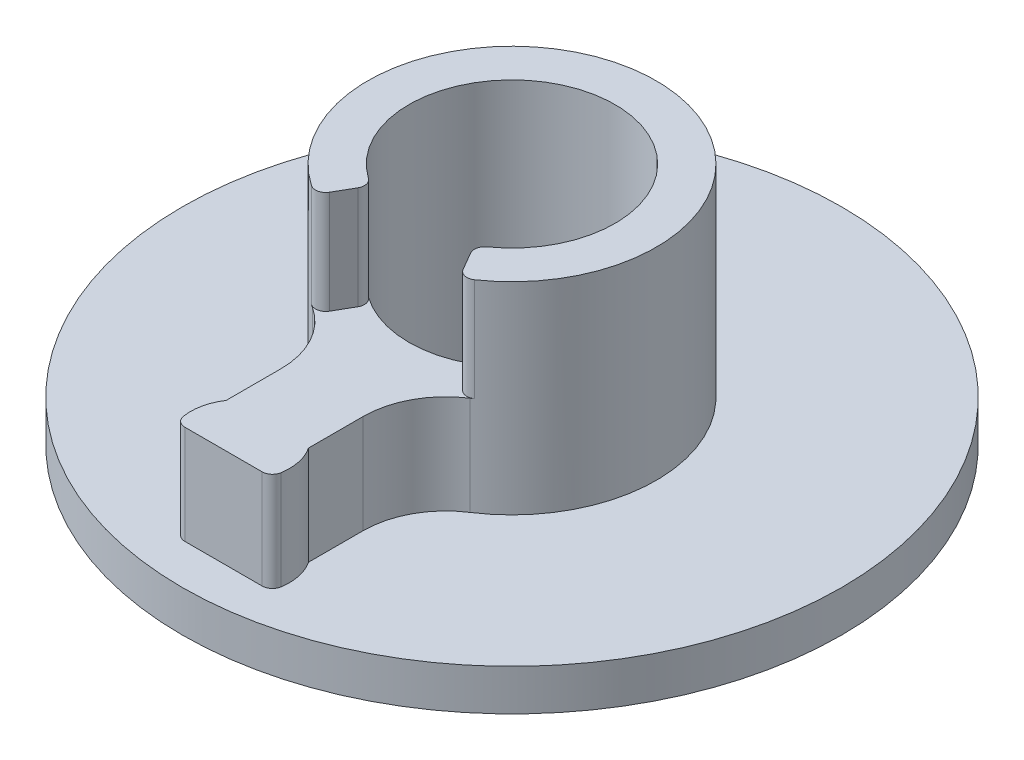
SolidWorks part; units mm, degrees
ref_plane "Plan de face" through (0, 0, 0) normal (0, 0, 1) x (1, 0, 0)
ref_plane "Plan de dessus" through (0, 0, 0) normal (0, 1, 0) x (1, 0, 0)
ref_plane "Plan de droite" through (0, 0, 0) normal (1, 0, 0) x (0, 0, -1)
sketch "Esquisse1" plane through (0, 0, 0) normal (0, 1, 0) x (1, 0, 0)
  line L18 (0, 9.2394) -> (0, -19.4288) construction
  circle A3 centre (0, 0) radius 2.5
  circle A7 centre (0, 0) radius 8
  point P1 (0, 0)
  point P2 (0, 0)
  point P3 (0, 0)
  point P4 (0, 0)
  point P5 (0, 0)
  point P7 (0, 0)
  point P8 (-1.5922, -5.6562)
  point P9 (1.577, -5.6853)
  point P10 (0, -8)
  point P11 (0, 0)
  point P12 (-0.0647, -8)
  point P30 (0, -8)
  point P31 (0, -8)
  dimension "D3" = 2.5
  dimension "D11" = 16
extrude "Boss.-Extru.1" add sketch "Esquisse1" along normal blind 1
sketch "Esquisse2" plane through (0, 1, 0) normal (0, 1, 0) x (1, 0, 0)
  line L0 (-1, -5.9367) -> (-1, -4.6098)
  line L1 (1, -5.9367) -> (1, -4.6098)
  line L2 (0, 5.8766) -> (0, -12.0862) construction
  line L3 (1.1314, -7) -> (-1.1314, -7)
  arc A0 (-1, -5.9367) -> (-1.1314, -7) centre (0, -6.6) ccw
  arc A1 (1.9091, -2.9335) -> (-1.9091, -2.9335) centre (0, 0) ccw
  circle A2 centre (0, 0) radius 2.5
  circle A3 centre (0, 0) radius 2.5 construction
  arc A4 (1.1314, -7) -> (1, -5.9367) centre (0, -6.6) ccw
  arc A5 (1.9091, -2.9335) -> (1, -4.6098) centre (3, -4.6098) ccw
  arc A6 (-1.9091, -2.9335) -> (-1, -4.6098) centre (-3, -4.6098) cw
  point P12 (0, 0)
  point P15 (0, 0)
  dimension "D4" = 1.2
  dimension "D6" = 2
  dimension "D1" = 7
  dimension "D2" = 7
  dimension "D3" = 6.6
  dimension "D5" = 1
extrude "Boss.-Extru.2" add sketch "Esquisse2" along normal blind 4.9
sketch "Esquisse4" plane through (0, 0, 0) normal (0, -1, 0) x (1, 0, 0)
  circle A0 centre (0, 0) radius 5.4
  circle A1 centre (0, 0) radius 4
  point P16 (0, 0)
  point P18 (0, 0)
  point P129 (0, 0)
  dimension "D1" = 8
  dimension "D2" = 10.8
extrude "Boss.-Extru.3" add sketch "Esquisse4" along normal blind 1.5
sketch "Esquisse5" plane through (0, 5.9, 0) normal (0, 1, 0) x (1, 0, 0)
  line L0 (-1.25, -2.1651) -> (-1.7569, -3.043)
  line L1 (1.25, -2.1651) -> (1.7569, -3.043)
  line L2 (0, 0) -> (0, -9.216) construction
  line L3 (-1, -5.9367) -> (-1, -4.6098)
  line L4 (1, -5.9367) -> (1, -4.6098)
  line L5 (0, 0) -> (-1.25, -2.1651) construction
  line L6 (0, 0) -> (1.25, -2.1651) construction
  line L8 (-1, -4.6098) -> (-1, -5.9367) construction
  line L9 (1, -5.9367) -> (1, -4.6098) construction
  line L10 (-1.1314, -7) -> (1.1314, -7)
  arc A0 (-1, -5.9367) -> (-1.1314, -7) centre (0, -6.6) ccw
  arc A1 (-1.25, -2.1651) -> (1.25, -2.1651) centre (0, 0) ccw
  circle A2 centre (0, 0) radius 2.5 construction
  arc A4 (1.1314, -7) -> (1, -5.9367) centre (0, -6.6) ccw construction
  arc A5 (1.1314, -7) -> (1, -5.9367) centre (0, -6.6) ccw
  arc A6 (1.7569, -3.043) -> (1, -4.6098) centre (3, -4.6098) ccw
  arc A7 (1.9091, -2.9335) -> (1, -4.6098) centre (3, -4.6098) ccw construction
  arc A8 (-1, -4.6098) -> (-1.7569, -3.043) centre (-3, -4.6098) ccw
  arc A9 (-1, -4.6098) -> (-1.9091, -2.9335) centre (-3, -4.6098) ccw construction
  dimension "D2" = 30
  dimension "D3" = 30
extrude "Enlèv. mat.-Extru.3" cut sketch "Esquisse5" against normal blind 2.5
fillet "Congé4" radius 0.25 6 edges at (-1.7569, 4.65, 3.043) (-1.25, 4.65, 2.1651) (1.25, 4.65, 2.1651) (1.7569, 4.65, 3.043) (-1.1314, 2.2, 7) (1.1314, 2.2, 7)
sketch "Esquisse6" plane through (0, -1.5, 0) normal (0, -1, 0) x (1, 0, 0)
  circle A0 centre (0, 0) radius 2.25
  circle A1 centre (0, 0) radius 3.25
  dimension "D1" = 6.5
  dimension "D2" = 4.5
extrude "Boss.-Extru.4" add sketch "Esquisse6" against normal blind 1.4 separate body
chamfer "Chanfrein1" distance 0.2 angle 30 1 edges at (0, -1.5, -5.4) first distance on face at (0, -1.5, -5.4)
